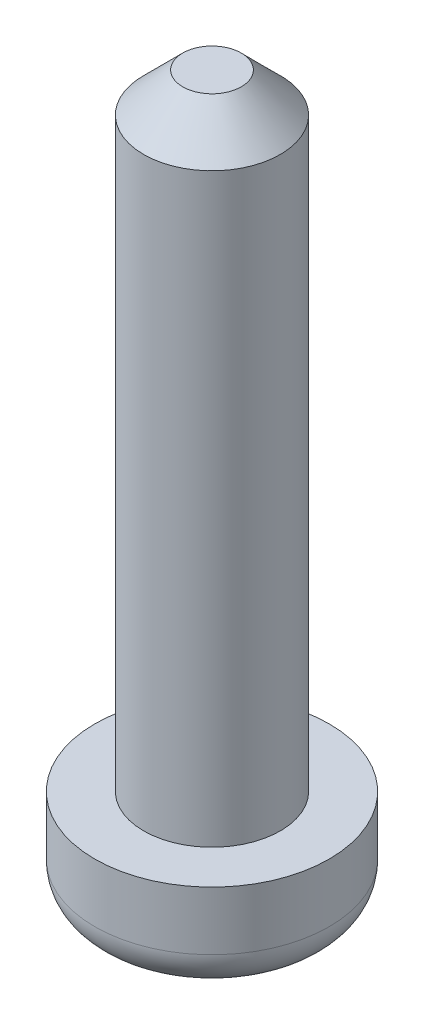
SolidWorks part; units mm, degrees
ref_plane "Vorne" through (0, 0, 0) normal (0, 0, 1) x (1, 0, 0)
ref_plane "Oben" through (0, 0, 0) normal (0, 1, 0) x (1, 0, 0)
ref_plane "Rechts" through (0, 0, 0) normal (1, 0, 0) x (0, 0, -1)
sketch "Skizze1" plane through (0, 0, 0) normal (0, 1, 0) x (1, 0, 0)
  circle A0 centre (0, 0) radius 1.75
  dimension "D1" = 3.5
extrude "Aufsatz-Linear austragen1" add sketch "Skizze1" along normal blind 16
sketch "Skizze2" plane through (0, 0, 0) normal (0, 1, 0) x (1, 0, 0)
  circle A0 centre (0, 0) radius 3
  dimension "D1" = 6
extrude "Aufsatz-Linear austragen2" add sketch "Skizze2" against normal blind 2.5
sketch "Skizze3" plane through (0, -2.5, 0) normal (0, -1, 0) x (1, 0, 0)
  line L0 (0, -3.3) -> (0, 3.3) construction
  line L1 (-0.5, 2) -> (0.5, 2)
  line L2 (-0.5, 2) -> (-0.5, 0.5)
  line L3 (-0.5, -2) -> (0.5, -2)
  line L4 (0.5, 2) -> (0.5, 0.5)
  line L5 (-2, 0.5) -> (-0.5, 0.5)
  line L6 (-2, 0.5) -> (-2, -0.5)
  line L7 (-2, -0.5) -> (-0.5, -0.5)
  line L8 (2, 0.5) -> (2, -0.5)
  line L9 (3.3, 0) -> (-3.3, 0) construction
  line L10 (0.5, 0.5) -> (2, 0.5)
  line L11 (-0.5, -0.5) -> (-0.5, -2)
  line L12 (0.5, -0.5) -> (2, -0.5)
  line L13 (0.5, -0.5) -> (0.5, -2)
  dimension "D1" = 1
  dimension "D2" = 4
  dimension "D3" = 2
  dimension "D4" = 2
  dimension "D5" = 0.5
  dimension "D6" = 0.5
extrude "Schnitt-Linear austragen1" cut sketch "Skizze3" against normal blind 1.5
fillet "Verrundung1" radius 1 1 edges at (0, -2.5, 3)
chamfer "Fase1" distance 1 angle 45 1 edges at (0, 16, 1.75)
